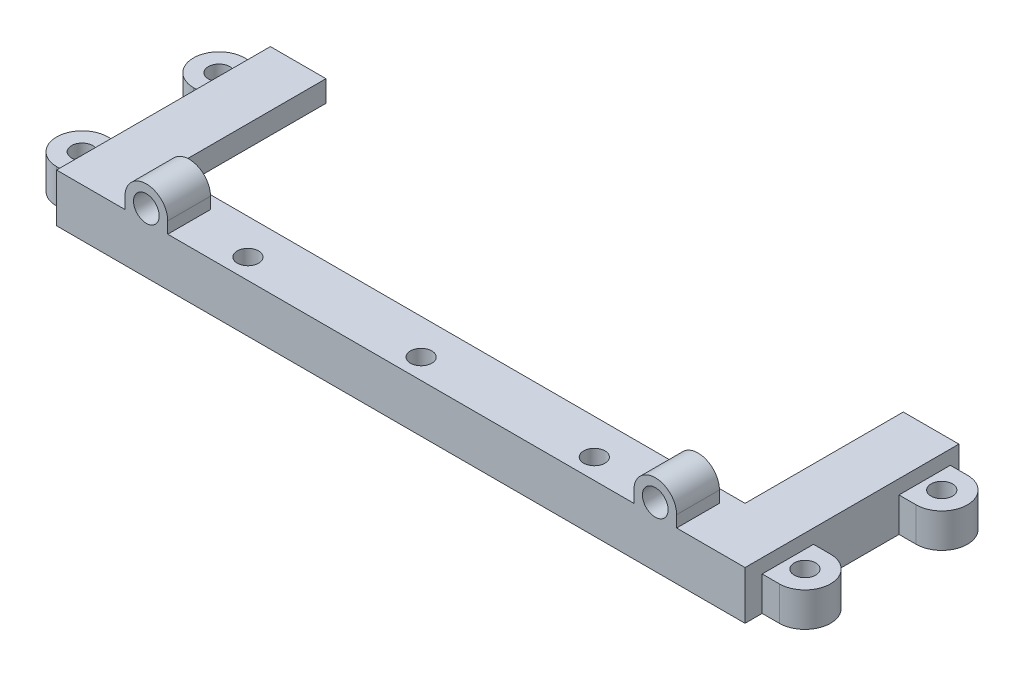
SolidWorks part; units mm, degrees
ref_plane "Alzado" through (0, 0, 0) normal (0, 0, 1) x (1, 0, 0)
ref_plane "Planta" through (0, 0, 0) normal (0, 1, 0) x (1, 0, 0)
ref_plane "Vista lateral" through (0, 0, 0) normal (1, 0, 0) x (0, 0, -1)
sketch "Croquis1" plane through (0, 0, 0) normal (0, 0, 1) x (1, 0, 0)
  line L0 (0, 0) -> (0, 11.3)
  line L1 (0, 11.3) -> (13, 11.3)
  line L2 (13, 11.3) -> (13, 6.3)
  line L3 (13, 6.3) -> (5, 6.3)
  line L4 (5, 6.3) -> (5, 0)
  line L5 (5, 0) -> (0, 0)
  dimension "D1" = 6.3
  dimension "D2" = 5
  dimension "D3" = 8
  dimension "D4" = 5
sketch "Croquis3" plane through (0, 0, 0) normal (0, 1, 0) x (1, 0, 0)
  line L0 (0, 0) -> (0, -37)
  dimension "D1" = 37
sweep "Barrer1" add profiles "Croquis1" path "Croquis3"
ref_plane "Plano1" through (80.5, 0, 0) normal (-1, 0, 0) x (0, 0, 1)
sketch "Croquis4" plane through (0, 0, 0) normal (-1, 0, 0) x (0, 0, 1)
  line L0 (0, 0) -> (37, 0) construction
  line L1 (37, 11.3) -> (50, 11.3)
  line L2 (37, 11.3) -> (37, 0)
  line L3 (37, 0) -> (50, 0)
  line L4 (50, 11.3) -> (50, 0)
  dimension "D1" = 13
extrude "Saliente-Extruir1" add sketch "Croquis4" against normal blind 161
mirror "Simetría5" about plane through (80.5, 0, 0) normal (-1, 0, 0) of "Barrer1"
sketch "Croquis5" plane through (0, 0, 0) normal (0, -1, 0) x (1, 0, 0)
  line L1 (5, 37) -> (156, 37)
  line L2 (5, 37) -> (5, 40.5)
  line L3 (5, 40.5) -> (156, 40.5)
  line L4 (156, 37) -> (156, 40.5)
  dimension "D1" = 3.5
  dimension "D2" = 151
extrude "Cortar-Extruir1" cut sketch "Croquis5" against normal blind 6.3
sketch "Croquis6" plane through (0, 0, 50) normal (0, 0, 1) x (1, 0, 0)
  line L0 (161, 11.3) -> (0, 11.3) construction
  line L1 (16, 11.3) -> (26, 11.3)
  line L2 (16, 11.3) -> (16, 14)
  line L4 (26, 11.3) -> (26, 14)
  line L5 (0, 0) -> (0, 11.3) construction
  arc A0 (26, 14) -> (16, 14) centre (21, 14) ccw
  dimension "D1" = 2.7
  dimension "D2" = 10
  dimension "D3" = 21
extrude "Saliente-Extruir2" add sketch "Croquis6" against normal blind 10
sketch "Croquis7" plane through (0, 0, 50) normal (0, 0, 1) x (1, 0, 0)
  circle A0 centre (21, 14) radius 3
  dimension "D1" = 6
extrude "Cortar-Extruir2" cut sketch "Croquis7" against normal through all
mirror "Simetría6" about plane through (80.5, 0, 0) normal (-1, 0, 0) of "Saliente-Extruir2", "Cortar-Extruir2"
sketch "Croquis8" plane through (0, 0, 0) normal (0, -1, 0) x (1, 0, 0)
  line L0 (161, 0) -> (161, 50) construction
  line L1 (161, 46) -> (165, 46)
  line L2 (161, 46) -> (161, 34)
  line L3 (161, 34) -> (165, 34)
  line L5 (161, 50) -> (0, 50) construction
  arc A0 (165, 34) -> (165, 46) centre (165, 40) ccw
  point P7 (0, 0)
  dimension "D1" = 4
  dimension "D2" = 12
  dimension "D3" = 10
extrude "Saliente-Extruir3" add sketch "Croquis8" against normal blind 8
sketch "Croquis9" plane through (0, 0, 0) normal (0, -1, 0) x (1, 0, 0)
  circle A0 centre (165, 40) radius 2.5
  dimension "D1" = 5
extrude "Cortar-Extruir3" cut sketch "Croquis9" against normal through all
ref_plane "Plano2" through (0, 0, 24) normal (0, 0, -1) x (-1, 0, 0)
mirror "Simetría7" about plane through (0, 0, 24) normal (0, 0, -1) of "Saliente-Extruir3", "Cortar-Extruir3"
mirror "Simetría8" about plane through (80.5, 0, 0) normal (-1, 0, 0) of "Simetría7", "Saliente-Extruir3", "Cortar-Extruir3"
sketch "Croquis10" plane through (0, 11.3, 0) normal (0, 1, 0) x (1, 0, 0)
  line L0 (161, -50) -> (161, 0) construction
  line L1 (135, -50) -> (26, -50) construction
  circle A0 centre (121, -45.25) radius 2.5
  dimension "D3" = 5
  dimension "D1" = 40
  dimension "D2" = 4.75
extrude "Cortar-Extruir4" cut sketch "Croquis10" against normal through all
pattern_linear "MatrizL1" count 3 spacing 40.5 along (-1, 0, 0) of "Cortar-Extruir4"
